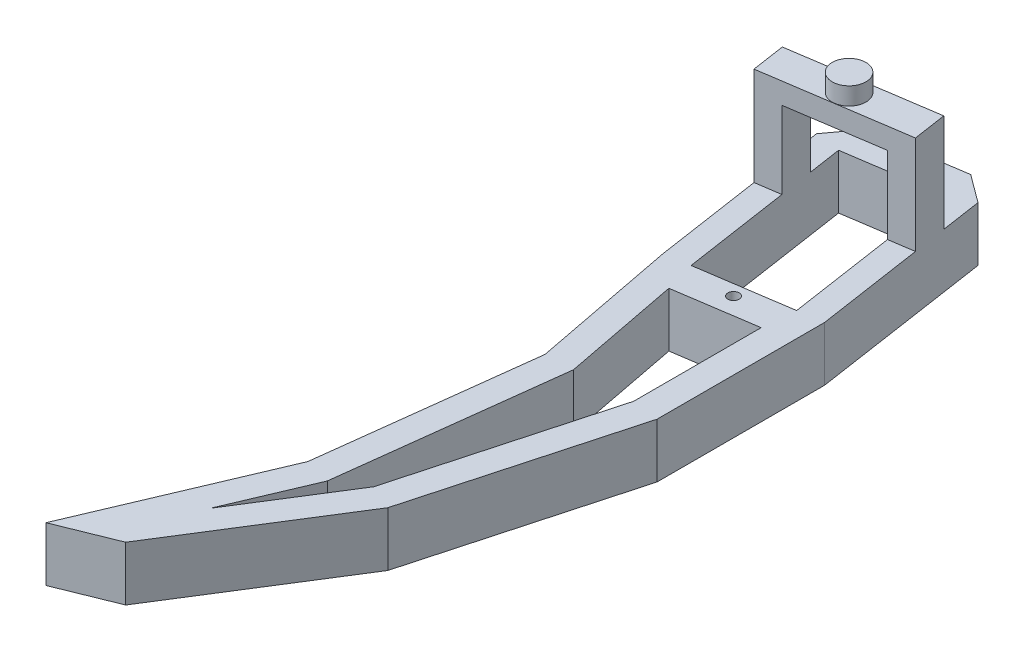
SolidWorks part; units mm, degrees
ref_plane "Front Plane" through (0, 0, 0) normal (0, 0, 1) x (1, 0, 0)
ref_plane "Top Plane" through (0, 0, 0) normal (0, 1, 0) x (1, 0, 0)
ref_plane "Right Plane" through (0, 0, 0) normal (1, 0, 0) x (0, 0, -1)
sketch "Sketch2" plane through (0, 0, 0) normal (0, 1, 0) x (1, 0, 0)
  line L0 (-16.722, -36.8947) -> (-23.8866, -53.7959)
  line L1 (-23.8866, -53.7959) -> (-18.6698, -51.6853)
  line L2 (-18.6698, -51.6853) -> (-9.3737, -36.8947)
  line L3 (-16.722, -36.8947) -> (-14.3508, -17.4669)
  line L4 (-9.3737, -36.8947) -> (-4.0462, -17.4713)
  line L5 (-14.3508, -17.4669) -> (-16.95, -4.011)
  line L6 (-4.0462, -17.4713) -> (-4.0462, -4.011)
  line L7 (-16.95, -4.011) -> (-4.0462, -4.011)
  line L8 (-13.9209, -6.511) -> (-6.5462, -6.511)
  line L9 (-6.5462, -17.1347) -> (-6.5462, -6.511)
  line L10 (-11.6869, -35.8772) -> (-6.5462, -17.1347)
  line L11 (-17.4878, -45.1066) -> (-11.6869, -35.8772)
  line L12 (-17.4878, -45.1066) -> (-17.4878, -45.1066)
  line L13 (-14.283, -37.5467) -> (-17.4878, -45.1066)
  line L14 (-14.283, -37.5467) -> (-11.8215, -17.3792)
  line L15 (-11.8215, -17.3792) -> (-13.9209, -6.511)
  dimension "D1" = 2.5
extrude "Boss-Extrude1" add sketch "Sketch2" along normal blind 5
scale "Scale2" scale about centroid uniform scaling yes scale factor 1.55
sketch "Sketch6" plane through (0, 6.375, 0) normal (0, 1, 0) x (1, 0, 0)
  line L3 (-14.6542, 4.6895) -> (-3.2234, 6.404)
  line L4 (-3.2234, 6.404) -> (-3.2234, 4.6895)
  line M11 (-14.6542, 4.6895) -> (-3.2234, 4.6895)
extrude "Cut-Extrude1" cut sketch "Sketch6" against normal blind 12.4 contours L4 L3 M11 region at (-7.0336, 6.375, -5.261)
ref_plane "Plane1" through (0, 5, 0) normal (0, 1, 0) x (1, 0, 0)
sketch "Sketch7" plane through (0, 6.375, 0) normal (0, 1, 0) x (1, 0, 0)
  line L0 (-19.3493, 8.5645) -> (0.6516, 8.5645)
  line L1 (0.6516, 8.5645) -> (0.6516, 11.5645)
  line L2 (-19.3493, 8.5645) -> (0.6516, 11.5645)
extrude "Boss-Extrude3" add sketch "Sketch7" against normal blind 7.75
sketch "Sketch9" plane through (-1.6821, 0, -11.2144) normal (-0.1483, 0, -0.9889) x (-0.9889, 0, 0.1483)
  line L1 (-2.3598, 6.375) -> (17.8649, 6.375)
  line L2 (-2.3598, 6.375) -> (-2.3598, -1.375)
  line L3 (-2.3598, -1.375) -> (17.8649, -1.375)
  line L4 (17.8649, 6.375) -> (17.8649, -1.375)
extrude "Boss-Extrude4" add sketch "Sketch9" along normal blind 29.5
sketch "Sketch10" plane through (0, 6.375, 0) normal (0, 1, 0) x (1, 0, 0)
  line L0 (-23.7252, 37.7381) -> (-3.7242, 40.7381)
  line L14 (-19.5964, 33.8071) -> (-6.518, 35.7687)
  line L19 (-23.7252, 37.7381) -> (-19.3493, 8.5645)
  line L20 (-3.7242, 40.7381) -> (0.6516, 11.5645)
  line L21 (-19.5964, 33.8071) -> (-15.888, 9.0836)
  line L23 (-6.518, 35.7687) -> (-2.8096, 11.0453)
  line L24 (-19.7447, 34.796) -> (-15.888, 9.0836) construction
  line L25 (-19.7447, 34.796) -> (-6.6663, 36.7577) construction
  line L26 (-6.6663, 36.7577) -> (-2.8096, 11.0453) construction
  line L27 (-23.0577, 33.2879) -> (-3.0567, 36.2879) construction
  line L28 (-15.888, 9.0836) -> (-2.8096, 11.0453)
  dimension "D1" = 4.5
  dimension "D2" = 3.5
extrude "Cut-Extrude2" cut sketch "Sketch10" against normal blind 12.4 contours L21 L28 L23 L14 region at (-11.203, 6.375, -22.4262)
fillet "Chamfer1" radius 3.5 1 edges at (-23.7252, 2.5, -37.7381) type face fillet profile chamfer first side face at (-21.5372, 2.5, -23.1513) second side face at (-13.7247, 2.5, -39.2381)
fillet "Chamfer2" radius 3.5 1 edges at (-3.7242, 2.5, -40.7381) type face fillet profile chamfer first side face at (-11.994, 2.5, -39.4977) second side face at (-1.5363, 2.5, -26.1513)
sketch "Sketch11" plane through (0, 6.375, 0) normal (0, 1, 0) x (1, 0, 0)
  line L0 (-13.0572, 34.7879) -> (-13.3168, 36.5185)
  line L1 (-19.5964, 33.8071) -> (-6.518, 35.7687) construction
  circle A0 centre (-13.3168, 36.5185) radius 0.8
extrude "Cut-Extrude3" cut sketch "Sketch11" against normal blind 12.4 contours A0
sketch "Sketch12" plane through (0, 6.375, 0) normal (0, 1, 0) x (1, 0, 0)
  line L0 (-9.3488, 10.0645) -> (-9.0893, 8.3338)
  line L1 (-15.888, 9.0836) -> (-2.8096, 11.0453) construction
  circle A0 centre (-9.0893, 8.3338) radius 0.8
extrude "Cut-Extrude4" cut sketch "Sketch12" against normal blind 12.4 contours A0
sketch "Sketch17" plane through (0, 6.375, 0) normal (0, 1, 0) x (1, 0, 0)
  line L0 (-13.0572, 34.7879) -> (-9.3488, 10.0645)
  line L1 (-19.5964, 33.8071) -> (-6.518, 35.7687) construction
  line L2 (-15.888, 9.0836) -> (-2.8096, 11.0453) construction
  line L3 (-17.7422, 21.4453) -> (-17.6384, 20.7531)
  line L4 (-19.5964, 33.8071) -> (-15.888, 9.0836) construction
  line L10 (-17.7422, 21.4453) -> (-19.4184, 32.6203)
  line L11 (-19.4184, 32.6203) -> (-22.8797, 32.1012)
  line L12 (-23.206, 34.2768) -> (-19.3493, 8.5645) construction
  line L13 (-17.6384, 20.7531) -> (-21.0997, 20.2339)
  line L14 (-22.8797, 32.1012) -> (-21.0997, 20.2339)
  line L15 (-6.34, 34.582) -> (-2.8787, 35.1012)
  line L16 (-4.6638, 23.407) -> (-6.34, 34.582)
  line L17 (-4.6638, 23.407) -> (-4.56, 22.7148)
  line L18 (-4.56, 22.7148) -> (-1.0987, 23.2339)
  line L19 (-2.8787, 35.1012) -> (-1.0987, 23.2339)
  line M3 (-15.888, 9.0836) -> (-19.5964, 33.8071)
  line M5 (-6.518, 35.7687) -> (-2.8096, 11.0453)
  line M7 (0.6516, 11.5645) -> (-3.205, 37.2768)
  line M11 (-23.206, 34.2768) -> (-19.3493, 8.5645)
  dimension "D1" = 0.7
  dimension "D2" = 11.175
extrude "Boss-Extrude5" add sketch "Sketch17" along normal blind 14 contours L13 L11 M3 M11 | L18 L15 M5 M7 region at (-20.259, 6.375, -26.4271) region at (-3.7193, 6.375, -28.908)
sketch "Sketch18" plane through (-14.206, 0, 2.1308) normal (0.9889, 0, -0.1483) x (-0.1483, 0, -0.9889)
  line L0 (23.1399, 20.375) -> (23.1399, 6.375) construction
  line L1 (35.1399, 20.375) -> (23.1399, 20.375)
  line L2 (35.1399, 20.375) -> (35.1399, 17.375)
  line L3 (35.1399, 17.375) -> (23.1399, 17.375)
  line L4 (23.1399, 20.375) -> (23.1399, 17.375)
  dimension "D1" = 3
extrude "Boss-Extrude6" add sketch "Sketch18" along normal blind 14
sketch "Sketch19" plane through (0, 20.375, 0) normal (0, 1, 0) x (1, 0, 0)
  circle A0 centre (-11.989, 27.694) radius 2.4
extrude "Boss-Extrude7" add sketch "Sketch19" along normal blind 2.5 contours A0
sketch "Sketch22" plane through (-17.6672, 0, 2.65) normal (-0.9889, 0, 0.1483) x (0.1483, 0, 0.9889)
  line L2 (-23.1399, 20.375) -> (-26.7399, 20.375)
  line L3 (-23.1399, 20.375) -> (-23.1399, 6.375)
  line L4 (-23.1399, 6.375) -> (-26.7399, 6.375)
  line L5 (-26.7399, 20.375) -> (-26.7399, 6.375)
  line L7 (-35.1399, 6.375) -> (-31.5399, 6.375)
  line L8 (-31.5399, 20.375) -> (-31.5399, 6.375)
  line L9 (-35.1399, 20.375) -> (-31.5399, 20.375)
  line L10 (-35.1399, 20.375) -> (-35.1399, 6.375)
  dimension "D1" = 14
  dimension "D2" = 3.6
extrude "Cut-Extrude5" cut sketch "Sketch22" against normal blind 21
